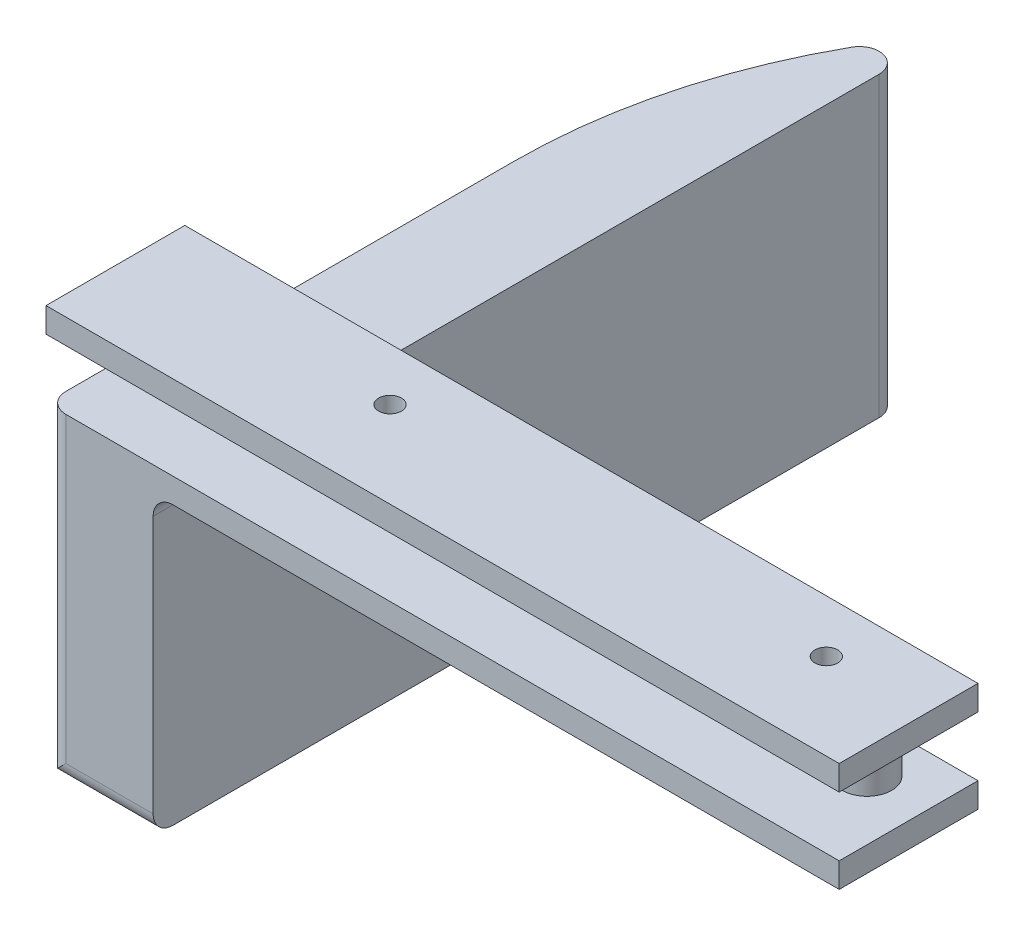
SolidWorks part; units mm, degrees
ref_plane "Front Plane" through (0, 0, 0) normal (0, 0, 1) x (1, 0, 0)
ref_plane "Top Plane" through (0, 0, 0) normal (0, 1, 0) x (1, 0, 0)
ref_plane "Right Plane" through (0, 0, 0) normal (1, 0, 0) x (0, 0, -1)
sketch "Sketch2" plane through (0, 0, 0) normal (0, 1, 0) x (1, 0, 0)
  line L1 (0, 0) -> (101.6, 0)
  line L2 (0, 0) -> (0, 17.78)
  line L3 (0, 17.78) -> (101.6, 17.78)
  line L4 (101.6, 0) -> (101.6, 17.78)
  dimension "D1" = 17.78
  dimension "D2" = 101.6
extrude "Boss-Extrude1" add sketch "Sketch2" along normal blind 3.175
sketch "Sketch3" plane through (0, 0, 0) normal (0, -1, 0) x (1, 0, 0)
  line L0 (93.98, -11.176) -> (5.08, -11.176) construction
  line L1 (93.98, -14.351) -> (5.08, -14.351)
  line L2 (93.98, -8.001) -> (5.08, -8.001)
  line L3 (0, 0) -> (101.6, 0) construction
  line L4 (0, -17.78) -> (0, 0) construction
  arc A0 (93.98, -14.351) -> (93.98, -8.001) centre (93.98, -11.176) ccw
  arc A1 (5.08, -8.001) -> (5.08, -14.351) centre (5.08, -11.176) ccw
  point P2 (49.53, -11.176)
  dimension "D1" = 88.9
  dimension "D2" = 11.176
  dimension "D3" = 5.08
  dimension "D4" = 6.35
extrude "Boss-Extrude2" add sketch "Sketch3" along normal blind 7.62 contours L2 A1 L1 A0
ref_plane "Plane1" through (0, -3.81, 0) normal (0, -1, 0) x (-1, 0, 0)
mirror "Mirror1" about plane through (0, -3.81, 0) normal (0, -1, 0) of "Boss-Extrude1"
sketch "Sketch5" plane through (0, -10.795, 0) normal (0, -1, 0) x (1, 0, 0)
  line L31 (0, 0) -> (13.7244, 0)
  line L32 (0, 0) -> (0, -59.8993)
  line L36 (13.7244, 0) -> (13.7244, -101.6)
  arc A2 (0, -59.8993) -> (13.7244, -101.6) centre (70.2144, -59.8993) ccw
  dimension "D1" = 101.6
extrude "Boss-Extrude3" add sketch "Sketch5" along normal blind 38.1
fillet "Fillet2" radius 2.54 1 edges at (13.7244, -29.845, -101.6)
fillet "Fillet3" radius 2.54 3 edges at (13.7244, -10.795, -8.89) (0, -28.2575, 0) (6.8622, -48.895, 0)
sketch "Sketch6" plane through (0, 3.175, 0) normal (0, 1, 0) x (1, 0, 0)
  line L0 (101.6, 17.78) -> (0, 17.78) construction
  line L1 (101.6, 0) -> (101.6, 17.78) construction
  circle A0 centre (88.9, 11.049) radius 1.4605
  circle A1 centre (33.02, 11.049) radius 1.4605
  dimension "D1" = 2.921
  dimension "D2" = 2.921
  dimension "D3" = 6.731
  dimension "D4" = 6.731
  dimension "D5" = 12.7
  dimension "D6" = 55.88
extrude "Cut-Extrude1" cut sketch "Sketch6" against normal through all
